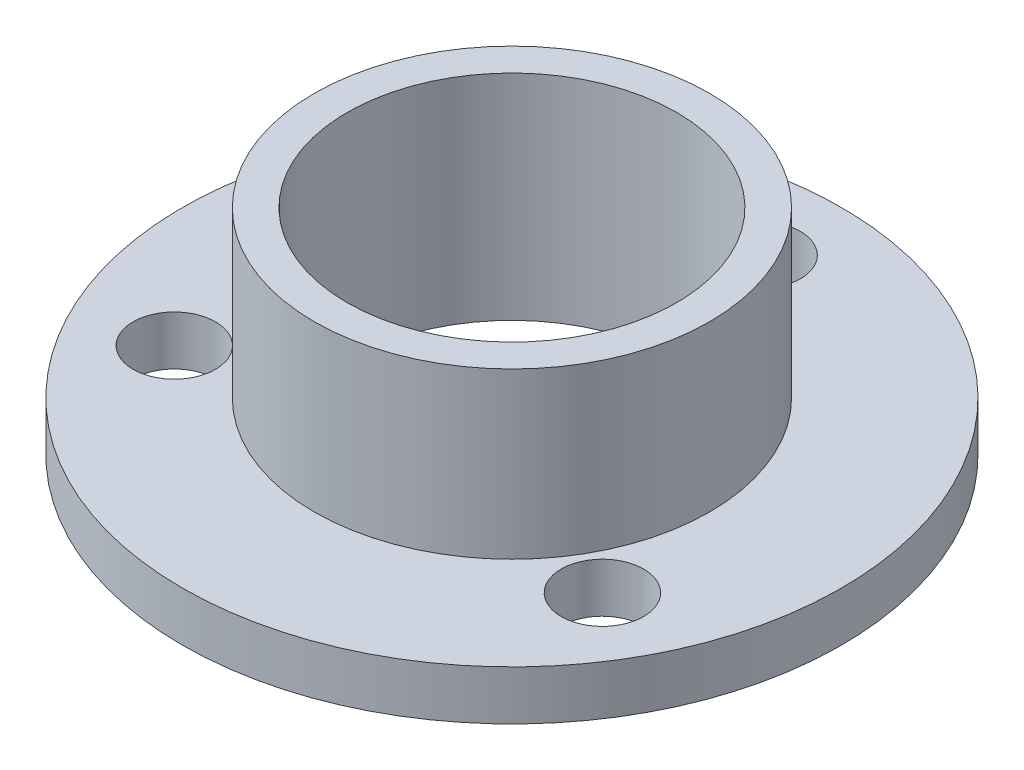
SolidWorks part; units mm, degrees
ref_plane "Front Plane" through (0, 0, 0) normal (0, 0, 1) x (1, 0, 0)
ref_plane "Top Plane" through (0, 0, 0) normal (0, 1, 0) x (1, 0, 0)
ref_plane "Right Plane" through (0, 0, 0) normal (1, 0, 0) x (0, 0, -1)
sketch "Sketch1" plane through (0, 0, 0) normal (0, 1, 0) x (1, 0, 0)
  circle A0 centre (0, 0) radius 10
  circle A1 centre (0, 0) radius 20
  circle A2 centre (0, 15) radius 2.5
  circle A3 centre (12.9904, -7.5) radius 2.5
  circle A4 centre (-12.9904, -7.5) radius 2.5
  circle A5 centre (0, 0) radius 12
  point P16 (0, 0)
  dimension "D1" = 10
  dimension "D2" = 3
  dimension "D3" = 2
extrude "Boss-Extrude1" add sketch "Sketch1" against normal blind 3 contours A1 A5 A4 A3 A2 | A5 A0 region at (-19.4343, 0, 0) region at (-11.6606, 0, 0)
extrude "Boss-Extrude2" add sketch "Sketch1<3>" along normal blind 10 contours A5 A0 region at (-11.6606, 0, 0)
sketch "Sketch1<3>" plane through (0, 0, 0) normal (0, 1, 0) x (1, 0, 0) same geometry as "Sketch1"
